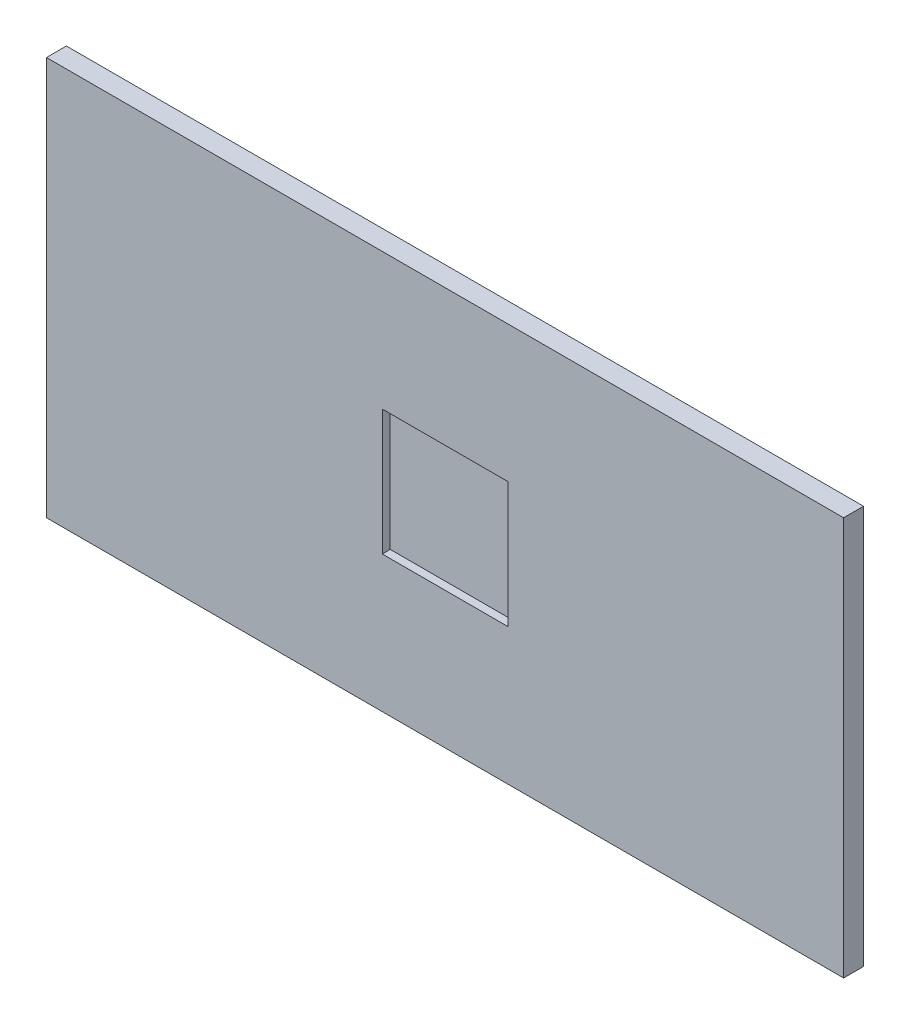
SolidWorks part; units mm, degrees
ref_plane "Front Plane" through (0, 0, 0) normal (0, 0, 1) x (1, 0, 0)
ref_plane "Top Plane" through (0, 0, 0) normal (0, 1, 0) x (1, 0, 0)
ref_plane "Right Plane" through (0, 0, 0) normal (1, 0, 0) x (0, 0, -1)
sketch "Sketch1" plane through (0, 0, 0) normal (0, 0, 1) x (1, 0, 0)
  line L0 (20, 10) -> (-20, -10) construction
  line L1 (-20, -10) -> (20, -10)
  line L2 (-20, -10) -> (-20, 10)
  line L3 (-20, 10) -> (20, 10)
  line L4 (20, -10) -> (20, 10)
  line L5 (-20, 10) -> (20, -10) construction
  line L6 (-3.15, 3.15) -> (3.15, -3.15) construction
  line L7 (-3.15, -3.15) -> (3.15, -3.15)
  line L8 (-3.15, -3.15) -> (-3.15, 3.15)
  line L9 (-3.15, 3.15) -> (3.15, 3.15)
  line L10 (3.15, -3.15) -> (3.15, 3.15)
  line L11 (3.15, 3.15) -> (-3.15, -3.15) construction
  point P0 (0, 0)
  point P6 (0, 0)
  point P11 (0, 0)
  point P14 (0, 0)
  dimension "D1" = 40
  dimension "D2" = 20
  dimension "D3" = 6.3
  dimension "D4" = 6.3
extrude "Boss-Extrude1" add sketch "Sketch1" along normal blind 1 contours L1 L4 L3 L2 L10 L7 L8 L9 | L7 L10 L9 L8 region at (-19.5528, 0, 0) region at (0, 0, 0)
extrude "PCB" cut sketch "Sketch1<3>" against normal blind 0.4 from surface contours L7 L10 L9 L8 region at (0, 0, 0) starting at face at (0, 0, 1)
sketch "Sketch1<3>" plane through (0, 0, 0) normal (0, 0, 1) x (1, 0, 0) same geometry as "Sketch1"
equation "\"pcb_length\"= 40 ' length of the chip in the direction of the feadline"
equation "\"pcb_side\"= 20    ' length of the chip in the other direction"
equation "\"pcb_width\"= 1"
equation "\"wall_width\"= 1  ' minimal width from the box walls"
equation "\"route_width\"= 1 ' The width of the trace on the lid for not touching the signal roates."
equation "\"route_clearence\"= 0.4 ' The clearence depth of the trace on the lid for not touching the signal roates."
equation "\"route_chip_clearence\"= 1"
equation "\"port_count\"= 2"
equation "\"port_space\"= 1.5"
equation "\"port_length\"= 5.1"
equation "\"port_width\"= 5.1"
equation "\"chip_length\"= 6.3 ' length of the chip in the direction of the feadline"
equation "\"chip_side\"= 6.3 ' length of the chip in the other direction"
equation "\"pedestal_depth\"= 1 ' depth of the pedestal under the chip"
equation "\"chip_leg\"= 0.8  ' size of the legs the chip lay on in case there is pedestal"
equation "\"wing_length\"= 10 ' Mounting wing size"
equation "\"wing_width\"= 1 ' mounting wing width"
equation "\"bonding_clearence\"= 1"
equation "\"box_height\"= \"wall_width\" + \"pedestal_depth\" + \"pcb_width\""
equation "\"box_length\"= \"pcb_length\" + 2 * \"wall_width\""
equation "\"box_side\"= \"pcb_side\" + 2 * \"wall_width\""
equation "\"D1@Sketch1\"=\"pcb_length\""
equation "\"D2@Sketch1\"=\"pcb_side\""
equation "\"D3@Sketch1\"=\"chip_length\""
equation "\"D1@Boss-Extrude1\"=\"pcb_width\""
equation "\"chip_width\"= 0.4 ' width of the chip"
equation "\"D1@PCB\" = \"chip_width\""
